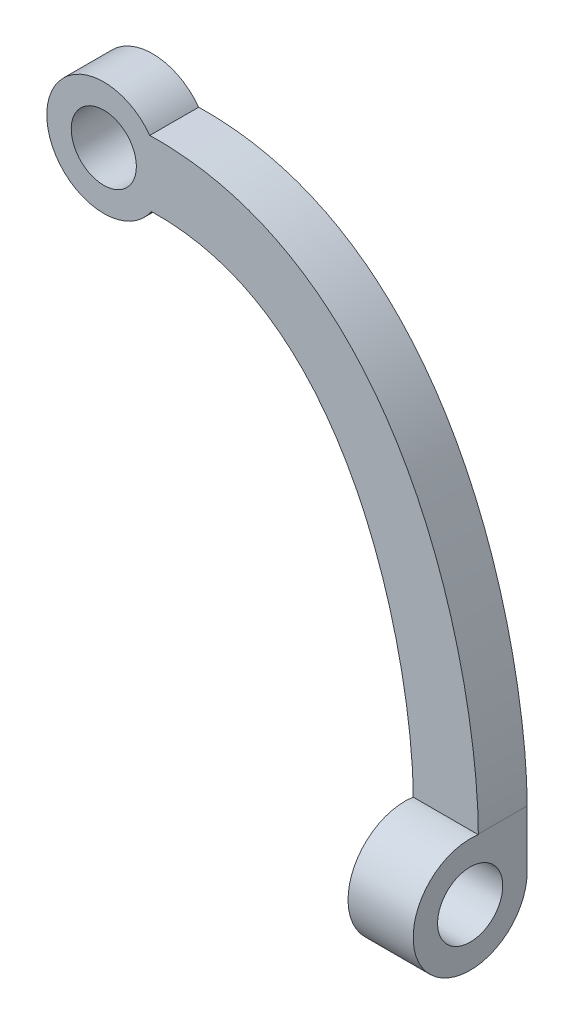
SolidWorks part; units mm, degrees
material "ABS"
ref_plane "Plano frontal" through (0, 0, 0) normal (0, 0, 1) x (1, 0, 0)
ref_plane "Plano superior" through (0, 0, 0) normal (0, 1, 0) x (1, 0, 0)
ref_plane "Plano direito" through (0, 0, 0) normal (1, 0, 0) x (0, 0, -1)
sketch "Esboço1" plane through (0, 0, 0) normal (0, 0, 1) x (1, 0, 0)
  line L0 (46, -7) -> (46, 6.9957)
  line L2 (38, 7) -> (38, -7)
  line L3 (38, -7) -> (46, -7)
  line L5 (38, 7) -> (46, -7) construction
  circle A3 centre (0, 57) radius 4
  arc A4 (5.6503, 61.1321) -> (5.8358, 53.1343) centre (0, 57) ccw
  spline S0 degree 3 poles (5.743, 57.1332) (35.3064, 57.819) (42.0071, 20.1914) (42, 6.9978) knots 0 0 0 0 1 1 1 1 construction
  spline S1 degree 1 poles (5.8358, 53.1343) (38, 7) knots 0 0 1 1 construction
  spline S2 degree 3 poles (5.8358, 53.1343) (6.2382, 53.1436) (7.0523, 53.1462) (8.6089, 53.0868) (10.474, 52.8976) (12.5771, 52.4993) (15.2208, 51.7556) (18.2494, 50.4514) (21.5153, 48.3428) (24.4538, 45.7353) (27.9571, 41.6673) (31.5674, 35.6448) (34.1793, 28.9568) (35.7182, 23.5956) (36.6148, 19.6673) (37.2723, 15.9304) (37.6381, 13.0591) (37.8325, 10.9601) (37.9322, 9.4976) (37.9794, 8.3879) (37.9974, 7.5653) (38.0001, 7.1916) (38, 7) knots 0 0 0 0 0.015625 0.03125 0.0625 0.09375 0.125 0.1875 0.25 0.3125 0.375 0.5 0.625 0.6875 0.75 0.8125 0.875 0.90625 0.9375 0.96875 0.984375 1 1 1 1
  spline S3 degree 1 poles (5.6503, 61.1321) (46, 6.9957) knots 0 0 1 1 construction
  spline S4 degree 3 poles (5.6503, 61.1321) (6.6607, 61.1556) (8.7108, 61.1208) (12.5789, 60.7276) (17.1279, 59.6558) (22.0402, 57.5393) (26.3943, 54.7224) (30.1926, 51.3436) (34.5586, 46.2609) (38.8155, 39.1125) (41.7607, 31.5455) (43.4705, 25.5873) (44.4596, 21.2523) (45.1839, 17.1358) (45.5892, 13.9579) (45.8072, 11.6053) (45.9205, 9.9496) (45.9863, 8.3917) (46.0003, 7.4709) (46, 6.9957) knots 0 0 0 0 0.03125 0.0625 0.125 0.1875 0.25 0.3125 0.375 0.5 0.625 0.6875 0.75 0.8125 0.875 0.90625 0.9375 0.96875 1 1 1 1
  point P17 (42, 0)
  dimension "D1" = 4
  dimension "D4" = 14
  dimension "D5" = 8
  dimension "D2" = 46
  dimension "D3" = 14
  dimension "D6" = 4
  dimension "D7" = 57
extrude "Ressalto-extrusão1" add sketch "Esboço1" along normal blind 14
sketch "Esboço2" plane through (46, 0, 0) normal (1, 0, 0) x (0, 0, -1)
  line L0 (-14, -7) -> (0, -7) construction
  line L1 (-14, -7) -> (-14, 6.9957) construction
  line L2 (-6, 64) -> (-6, 6.9282)
  line L3 (0, 64) -> (-14, 64) construction
  line L4 (-6, 64) -> (0, 64)
  line L5 (-6, 64) -> (-14, 64)
  line L6 (0, 64) -> (0, 0)
  line L7 (-14, 64) -> (-14, 0)
  circle A0 centre (-7, 0) radius 7
  circle A1 centre (-7, 0) radius 4
  line M19 (0, -7) -> (0, 6.9957)
  line M20 (0, 6.9957) -> (-14, 6.9957)
  line M21 (-14, 6.9957) -> (-14, -7)
  line M22 (-14, -7) -> (0, -7)
  dimension "D1" = 14
  dimension "D2" = 8
  dimension "D3" = 6
extrude "Corte-extrusão1" cut sketch "Esboço2" against normal through all contours A0 M21 M22 | A0 M20 M21 | A1 | A0 M22 M19 | A0 L2 M20 | A0 L2 L5 L7 M20
